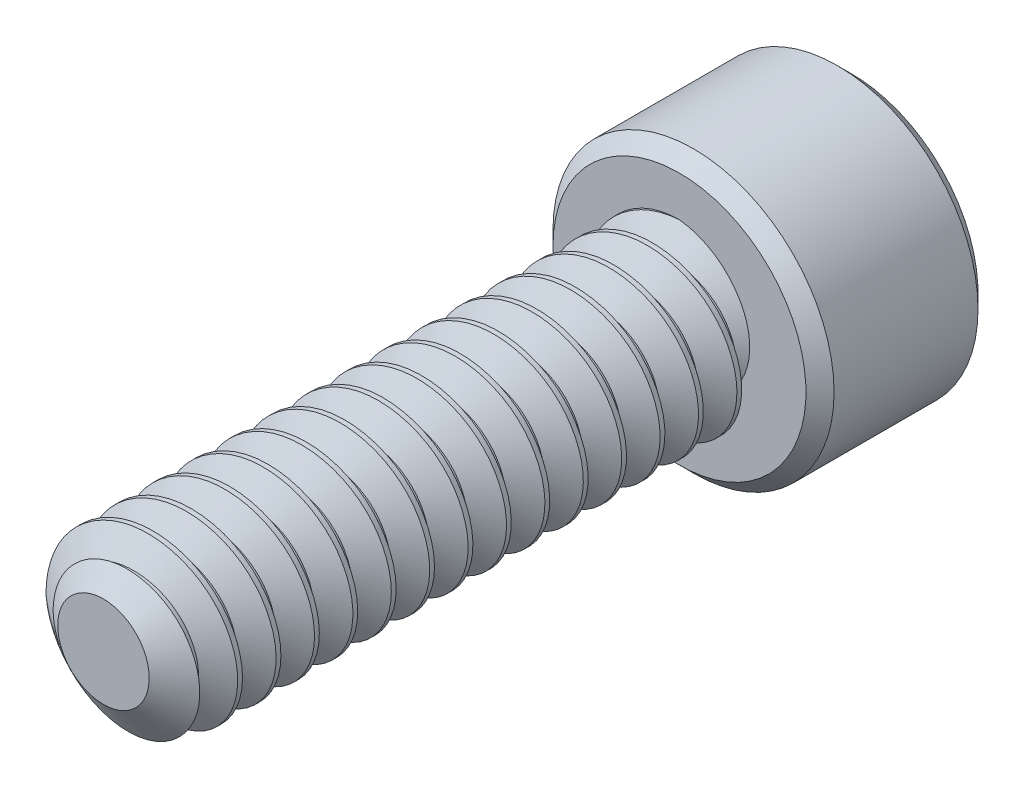
SolidWorks part; units mm, degrees
other "DetailItem1"
ref_plane "Front Plane" through (0, 0, 0) normal (0, 0, 1) x (1, 0, 0)
ref_plane "Top Plane" through (0, 0, 0) normal (0, 1, 0) x (1, 0, 0)
ref_plane "Right Plane" through (0, 0, 0) normal (1, 0, 0) x (0, 0, -1)
sketch "Sketch1" plane through (0, 0, 0) normal (0, 0, 1) x (1, 0, 0)
  circle A0 centre (0, 0) radius 1.4224
  dimension "OD" = 2.8448
extrude "Extrude1" add sketch "Sketch1" against normal blind 9.525
sketch "Sketch2" plane through (0, 0, 0) normal (0, 0, 1) x (1, 0, 0)
  circle A0 centre (0, 0) radius 1.4224 construction
  circle A1 centre (0, 0) radius 1.4224
curve "Helix/Spiral1" pitch 0.635 height 10.16 radius 1.4224 centre (0, 0, 0) axis (0, 0, -1) start towards (0, 1, 0) parameters "pitch"=0.635
sketch "Sketch3" plane through (0, 0, 0) normal (1, 0, 0) x (0, 0, -1)
  line L0 (-0.5556, 1.4224) -> (-0.3175, 1.01)
  line L1 (-0.3175, 1.01) -> (-0.2381, 1.01)
  line L2 (-0.2381, 1.01) -> (0, 1.4224)
  line L3 (-0.5556, 1.4224) -> (0, 1.4224)
  line L4 (-0.2778, 1.4224) -> (-0.2778, 1.01) construction
  line L5 (-0.4366, 1.2162) -> (-0.1191, 1.2162) construction
  line L6 (0, 1.4224) -> (0, -1.4224) construction
  dimension "D1" = 0.0794
  dimension "D2" = 0.3175
  dimension "D3" = 60
sweep "Cut-Sweep1" cut profiles "Sketch3" path "Helix/Spiral1"
sketch "Sketch4" plane through (0, 0, 0) normal (1, 0, 0) x (0, 0, -1)
  line L0 (0.4666, 1.4224) -> (0, 0.756)
  line L1 (0, 0.756) -> (0, 1.4224)
  line L2 (0.4666, 1.4224) -> (0, 1.4224)
  line L3 (-0.5556, 1.4224) -> (0, 1.4224) construction
  line L4 (0, 0) -> (7.0209, 0) construction
  dimension "D1" = 55
  dimension "D2" = 0.254
revolve "Cut-Revolve1" cut sketch "Sketch4" angle 360 about L4
sketch "Sketch5" plane through (0, 0, 0) normal (1, 0, 0) x (0, 0, -1)
  line L0 (9.525, -1.0232) -> (9.525, 1.0149) construction
  line L1 (9.525, 1.5494) -> (0.1202, 1.5494)
  line L2 (9.525, 1.5494) -> (9.525, 0)
  line L3 (9.525, 0) -> (0, 0)
  line L4 (0, 1.2192) -> (0, 0)
  line L5 (0.1202, 1.5494) -> (0, 1.2192)
  line L6 (0, 0) -> (9.9695, 0) construction
  point P3 (0, 1.5494)
  point P10 (0, 1.5494)
  dimension "D1" = 0.3302
  dimension "D2" = 0.127
  dimension "D3" = 20
  dimension "Min Thread" = 0
revolve "partially thread" [suppressed] add sketch "Sketch5" angle 360 about L6
sketch "Sketch6" plane through (0, 0, -9.525) normal (0, 0, -1) x (-1, 0, 0)
  circle A0 centre (0, 0) radius 2.3241
  dimension "head dia" = 4.6482
extrude "Extrude2" add sketch "Sketch6" along normal blind 2.8448
sketch "Sketch7" plane through (0, 0, -12.3698) normal (0, 0, -1) x (-1, 0, 0)
  line L1 (0, 1.3748) -> (-1.1906, 0.6874)
  line L2 (-1.1906, 0.6874) -> (-1.1906, -0.6874)
  line L3 (-1.1906, -0.6874) -> (0, -1.3748)
  line L4 (0, -1.3748) -> (1.1906, -0.6874)
  line L5 (1.1906, -0.6874) -> (1.1906, 0.6874)
  line L6 (1.1906, 0.6874) -> (0, 1.3748)
  circle A0 centre (0, 0) radius 1.1906 construction
  dimension "hex dia" = 2.3813
extrude "Cut-Extrude1" cut sketch "Sketch7" against normal blind 1.7859
sketch "Sketch8" plane through (0, 0, -12.3698) normal (0, 0, -1) x (-1, 0, 0)
  circle A0 centre (0, 0) radius 1.3748
extrude "Cut-Extrude2" cut sketch "Sketch8" against normal through all draft 45
chamfer "Chamfer1" distance 0.2324 angle 45 2 edges at (-2.3241, 0, -12.3698) (-2.3241, 0, -9.525)
sketch "Sketch9" plane through (0, 0, 0) normal (1, 0, 0) x (0, 0, -1)
  line L0 (0, 1.4224) -> (0, -1.4224) construction
  line L1 (1.5875, 1.4224) -> (1.5875, -1.4224) construction
  dimension "D1" = 1.5875
  dimension "D4" = 0.635
  dimension "D5" = 0.3302
equation "\"D3@Helix/Spiral1\" = \"screw length@Extrude1\"+\"pitch@Helix/Spiral1\""
equation "\"D1@Sketch3\" = \"pitch@Helix/Spiral1\"*.125"
equation "\"D2@Sketch3\" = \"pitch@Helix/Spiral1\"*.5"
equation "\"D1@Cut-Extrude1\" = \"hex dia@Sketch7\"*.75"
equation "\"D1@Chamfer1\" = \"head dia@Sketch6\"*.05"
equation "\"D1@Sketch9\" = \"pitch@Helix/Spiral1\"*2.5"
